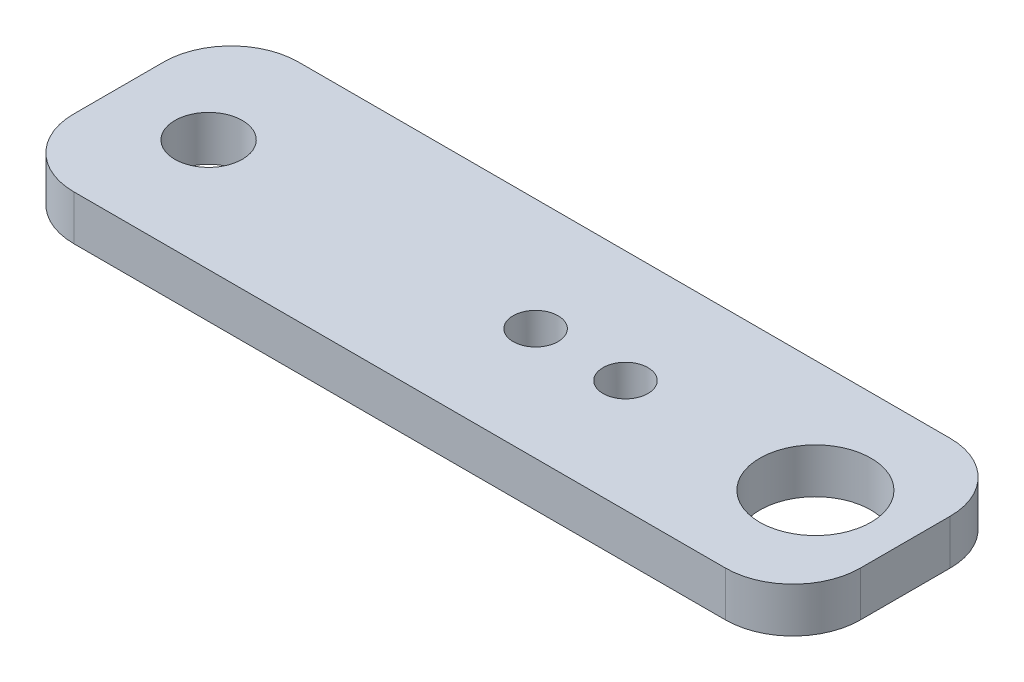
SolidWorks part; units mm, degrees
ref_plane "Front Plane" through (0, 0, 0) normal (0, 0, 1) x (1, 0, 0)
ref_plane "Top Plane" through (0, 0, 0) normal (0, 1, 0) x (1, 0, 0)
ref_plane "Right Plane" through (0, 0, 0) normal (1, 0, 0) x (0, 0, -1)
sketch "Sketch1" plane through (0, 0, 0) normal (0, 1, 0) x (1, 0, 0)
  line L1 (-17.5, 5) -> (17.5, 5)
  line L2 (-17.5, 5) -> (-17.5, -5)
  line L3 (-17.5, -5) -> (17.5, -5)
  line L4 (17.5, 5) -> (17.5, -5)
  line L5 (-17.5, 5) -> (17.5, -5) construction
  line L6 (-17.5, -5) -> (17.5, 5) construction
  point P0 (0, 0)
  dimension "D1" = 10
  dimension "D2" = 35
extrude "Boss-Extrude1" add sketch "Sketch1" along normal blind 2
sketch "Sketch2" plane through (0, 2, 0) normal (0, 1, 0) x (1, 0, 0)
  line L0 (13.5, 5) -> (13.5, -5) construction
  line L1 (-17.5, -5) -> (17.5, -5) construction
  line L2 (17.5, -5) -> (17.5, 5) construction
  circle A0 centre (13.5, 0) radius 2.4729
  circle A3 centre (5.05, 0) radius 1
  circle A4 centre (1.05, 0) radius 1
  point P10 (13.5, 0)
  dimension "D1" = 8.45
  dimension "D4" = 2
  dimension "D2" = 4
  dimension "D3" = 4
extrude "Cut-Extrude1" cut sketch "Sketch2" against normal blind 3
fillet "Fillet1" radius 3 4 edges at (17.5, 1, 5) (17.5, 1, -5) (-17.5, 1, -5) (-17.5, 1, 5)
hole_wizard "Ø3.0 (3) Diameter Hole1" positions "Sketch3" profile "Sketch4" hole size "Ø3.0" standard "BSI" end condition through all
sketch "Sketch3" plane through (0, 2, 0) normal (0, 1, 0) x (1, 0, 0)
  line L0 (-17.5, 2) -> (-17.5, -2) construction
  point P0 (-13.5, 0)
  dimension "D1" = 4
sketch "Sketch4" plane through (-13.5, 2, 0) normal (1, 0, 0) x (0, 0, 1)
  line L0 (0, 0) -> (0, 2)
  line L1 (0, 2) -> (1.5, 2)
  line L2 (1.5, 2) -> (1.5, 0)
  line L5 (1.5, 0) -> (0, 0)
  line L11 (0, -6.35) -> (0, 107.95) construction
  dimension "Thru Hole Dia." = 3
  dimension "Thru Hole Depth" = 2
